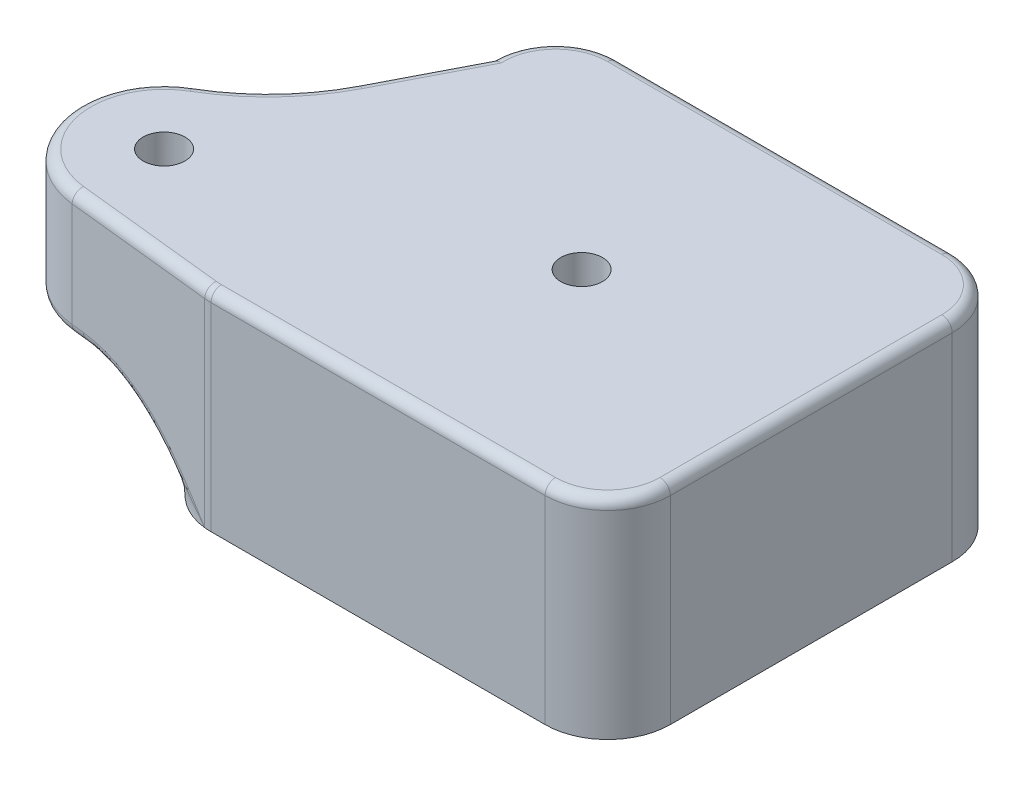
SolidWorks part; units mm, degrees
ref_plane "Front Plane" through (0, 0, 0) normal (0, 0, 1) x (1, 0, 0)
ref_plane "Top Plane" through (0, 0, 0) normal (0, 1, 0) x (1, 0, 0)
ref_plane "Right Plane" through (0, 0, 0) normal (1, 0, 0) x (0, 0, -1)
sketch "Sketch1" plane through (0, 0, 0) normal (0, 1, 0) x (1, 0, 0)
  line L0 (-11, 6.75) -> (-11, -6.75)
  line L1 (-8, 7.75) -> (8, 7.75)
  line L2 (-9, 6.75) -> (-9, -6.75)
  line L3 (-8, -7.75) -> (8, -7.75)
  line L4 (9, 6.75) -> (9, -6.75)
  line L5 (-9, 7.75) -> (9, -7.75) construction
  line L6 (-9, -7.75) -> (9, 7.75) construction
  line L7 (-8, -9.75) -> (8, -9.75)
  line L8 (11, 6.75) -> (11, -6.75)
  line L9 (-8, 9.75) -> (8, 9.75)
  arc A0 (-9, -6.75) -> (-8, -7.75) centre (-8, -6.75) ccw
  arc A1 (8, -7.75) -> (9, -6.75) centre (8, -6.75) ccw
  arc A2 (8, 7.75) -> (9, 6.75) centre (8, 6.75) cw
  arc A3 (-8, 7.75) -> (-9, 6.75) centre (-8, 6.75) ccw
  arc A4 (-11, -6.75) -> (-8, -9.75) centre (-8, -6.75) ccw
  arc A5 (8, -9.75) -> (11, -6.75) centre (8, -6.75) ccw
  arc A6 (8, 9.75) -> (11, 6.75) centre (8, 6.75) cw
  arc A7 (-8, 9.75) -> (-11, 6.75) centre (-8, 6.75) ccw
  point P0 (0, 0)
  dimension "D3" = 1
  dimension "D1" = 15.5
  dimension "D2" = 18
  dimension "D4" = 2
extrude "Boss-Extrude1" add sketch "Sketch1" along normal blind 5
sketch "Sketch2" plane through (0, 5, 0) normal (0, 1, 0) x (1, 0, 0)
  line L4 (-11, 6.75) -> (-11, -6.75)
  line L5 (-8, -9.75) -> (8, -9.75)
  line L6 (11, -6.75) -> (11, 6.75)
  line L7 (8, 9.75) -> (-8, 9.75)
  line L8 (-11, 6.75) -> (-11, -6.75)
  line L9 (-8, -9.75) -> (8, -9.75)
  line L10 (11, -6.75) -> (11, 6.75)
  line L11 (8, 9.75) -> (-8, 9.75)
  circle A0 centre (0, 0) radius 1
  arc A4 (-8, 9.75) -> (-11, 6.75) centre (-8, 6.75) ccw
  arc A5 (-11, -6.75) -> (-8, -9.75) centre (-8, -6.75) ccw
  arc A6 (8, -9.75) -> (11, -6.75) centre (8, -6.75) ccw
  arc A7 (11, 6.75) -> (8, 9.75) centre (8, 6.75) ccw
  arc A8 (-8, 9.75) -> (-11, 6.75) centre (-8, 6.75) ccw
  arc A9 (-11, -6.75) -> (-8, -9.75) centre (-8, -6.75) ccw
  arc A10 (8, -9.75) -> (11, -6.75) centre (8, -6.75) ccw
  arc A11 (11, 6.75) -> (8, 9.75) centre (8, 6.75) ccw
  dimension "D2" = 2
  dimension "D1" = 0
extrude "Boss-Extrude2" add sketch "Sketch2" along normal blind 5
sketch "Sketch3" plane through (0, 10, 0) normal (0, 1, 0) x (1, 0, 0)
  line L0 (-11, 6.75) -> (-11, -6.75) construction
  line L1 (-11, 6.75) -> (-11, -6.75)
  line L2 (-13.1998, 2.4879) -> (-11, 6.75)
  line L3 (-15.423, -8.9776) -> (-8.3172, -9.7332)
  circle A0 centre (-15, -5) radius 1
  circle A1 centre (0, 0) radius 1 construction
  arc A2 (-17.0246, -1.5502) -> (-15.423, -8.9776) centre (-15, -5) ccw
  arc A3 (-11, -6.75) -> (-8, -9.75) centre (-8, -6.75) ccw construction
  arc A4 (-11, -6.75) -> (-8.3172, -9.7332) centre (-8, -6.75) ccw
  circle A5 centre (-15, -5) radius 4 construction
  arc A6 (-13.1998, 2.4879) -> (-17.0246, -1.5502) centre (-22.086, 7.0743) cw
  point P16 (-15, -1)
  dimension "D2" = 15
  dimension "D3" = 2
  dimension "D5" = 10
  dimension "D1" = 5
  dimension "D4" = 3
extrude "Boss-Extrude3" add sketch "Sketch3" against normal blind 6
fillet "Fillet1" radius 4 2 edges at (-10.2307, 4, 8.756) (-11, 4, 0)
fillet "Fillet2" radius 0.5 19 edges at (-8.7071, 0, -7.4571) (0, 0, -7.75) (8.7071, 0, -7.4571) (9, 0, 0) (8.7071, 0, 7.4571) (0, 0, 7.75) (-8.7071, 0, 7.4571) (-12.0999, 10, -4.6189) (-14.8258, 10, -0.1976) (-18.9101, 10, 5.8432) (-11.8701, 10, 9.3554) (-8.1588, 10, 9.7458) (0, 10, 9.75) (10.1213, 10, 8.8713) (11, 10, 0) (10.1213, 10, -8.8713) (-10.1213, 10, -8.8713) (-9, 0, 0) (0, 10, -9.75)
fillet "Fillet3" radius 0.5 6 edges at (-12.8661, 3.696, 9.2495) (-15.0146, 4, 9.021) (-18.9101, 4, 5.8432) (-15.9619, 4, 0.8311) (-11.5941, 2.0975, -5.599)
